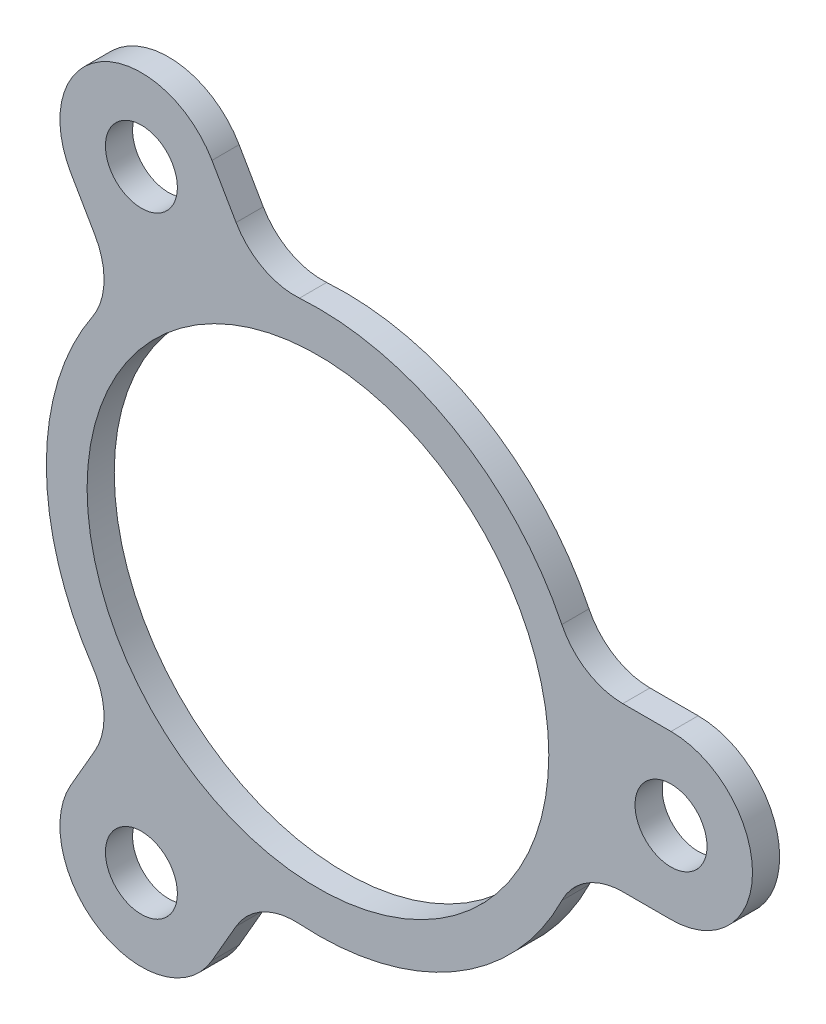
SolidWorks part; units mm, degrees
material "Alloy Steel"
ref_plane "Front Plane" through (0, 0, 0) normal (0, 0, 1) x (1, 0, 0)
ref_plane "Top Plane" through (0, 0, 0) normal (0, 1, 0) x (1, 0, 0)
ref_plane "Right Plane" through (0, 0, 0) normal (1, 0, 0) x (0, 0, -1)
ref_plane "Plane1" through (0, 0, 94.7) normal (0, 0, 1) x (1, 0, 0)
sketch "Sketch1" plane through (0, 0, 94.7) normal (0, 0, 1) x (1, 0, 0)
  line L0 (0, 0) -> (26, 0) construction
  line L1 (26, 6) -> (19.0788, 6)
  line L2 (26, -6) -> (19.0788, -6)
  line L3 (-7.8038, -25.5167) -> (-4.3432, -19.5227)
  line L4 (-18.1962, -19.5167) -> (-14.7355, -13.5227)
  line L5 (-18.1962, 19.5167) -> (-14.7355, 13.5227)
  line L6 (-7.8038, 25.5167) -> (-4.3432, 19.5227)
  circle A1 centre (26, 0) radius 3 construction
  circle A2 centre (0, 0) radius 17
  arc A4 (26, 6) -> (26, -6) centre (26, 0) cw
  arc A5 (-14.7355, 13.5227) -> (-14.7355, -13.5227) centre (0, 0) ccw
  arc A6 (-7.8038, -25.5167) -> (-18.1962, -19.5167) centre (-13, -22.5167) cw
  arc A7 (-18.1962, 19.5167) -> (-7.8038, 25.5167) centre (-13, 22.5167) cw
  arc A8 (19.0788, 6) -> (-4.3432, 19.5227) centre (0, 0) ccw
  arc A9 (-4.3432, -19.5227) -> (19.0788, -6) centre (0, 0) ccw
  point P0 (26, 0)
  point P4 (-13, -22.5167)
  point P5 (-13, 22.5167)
  point P6 (0, 0)
  point P11 (32, 0)
  dimension "D3" = 6
  dimension "D4" = 34
  dimension "D5" = 40
  dimension "D6" = 6
  dimension "D7" = 6
  dimension "D2" = 26
  dimension "D1" = 3
  dimension "D8" = 3
extrude "Boss-Extrude1" add sketch "Sketch1" along normal blind 2 contours A4 A2 region at (31.2282, 0, 94.7)
hole_wizard "M5 Clearance Hole1" positions "Sketch2" profile "Sketch4" hole size "M5" standard "ANSI Metric" end condition through all
sketch "Sketch2" plane through (0, 0, 96.7) normal (0, 0, 1) x (1, 0, 0)
  point P0 (-13, 22.5167)
  point P3 (26, 0)
  point P6 (-13, -22.5167)
sketch "Sketch4" plane through (-13, 22.5167, 96.7) normal (1, 0, 0) x (0, -1, 0)
  line L0 (0, 0) -> (0, 2)
  line L1 (0, 2) -> (2.65, 2)
  line L2 (2.65, 2) -> (2.65, 0)
  line L5 (2.65, 0) -> (0, 0)
  line L11 (0, -6.35) -> (0, 107.95) construction
  dimension "Thru Hole Dia." = 5.3
  dimension "Thru Hole Depth" = 2
fillet "Fillet1" radius 5 6 edges at (-4.3432, -19.5227, 95.7) (19.0788, -6, 95.7) (19.0788, 6, 95.7) (-4.3432, 19.5227, 95.7) (-14.7355, 13.5227, 95.7) (-14.7355, -13.5227, 95.7)
